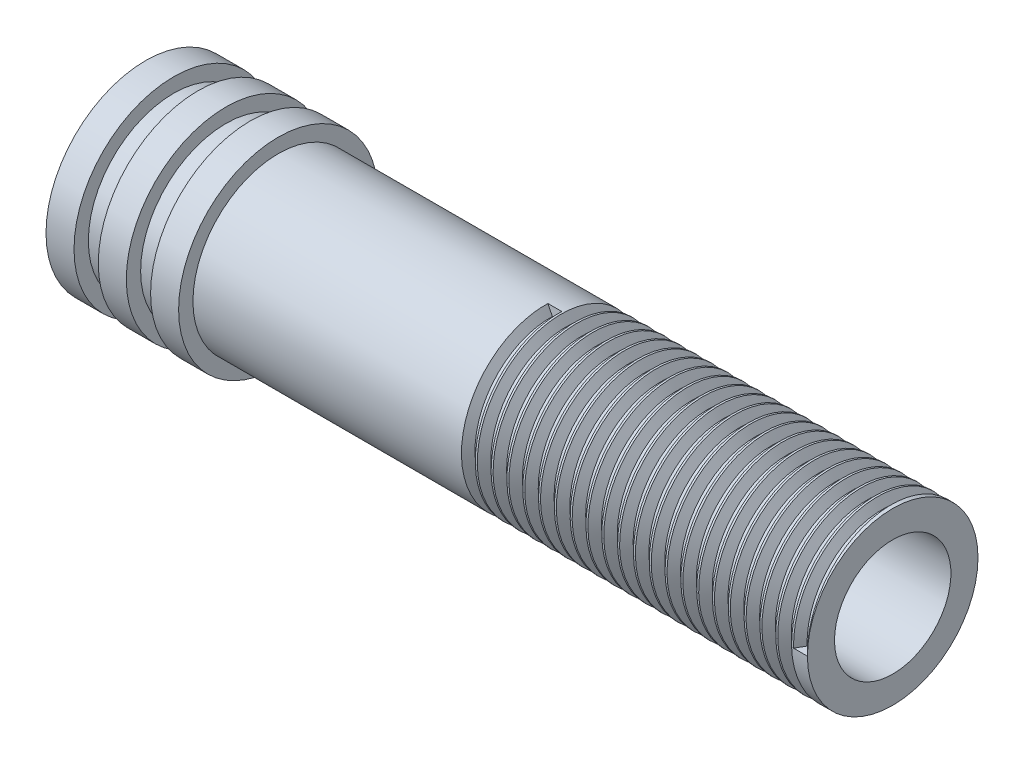
SolidWorks part; units mm, degrees
material "6061 Alloy"
ref_plane "Płaszczyzna przednia" through (0, 0, 0) normal (0, 0, 1) x (1, 0, 0)
ref_plane "Płaszczyzna górna" through (0, 0, 0) normal (0, 1, 0) x (1, 0, 0)
ref_plane "Płaszczyzna prawa" through (0, 0, 0) normal (1, 0, 0) x (0, 0, -1)
sketch "Szkic1" plane through (0, 0, 0) normal (0, 0, 1) x (1, 0, 0)
  line L0 (0, 0) -> (98.6784, 0)
  line L2 (10.7572, 0) -> (18.7572, 0)
  line L16 (72.2243, 0) -> (18.7572, 0)
  line L17 (-44.536, 13.7) -> (-44.536, 16.45)
  line L24 (-46.486, 13.7) -> (-42.586, 13.7)
  line L31 (0, 0) -> (-55.4823, 0)
  line L32 (-42.586, 13.7) -> (-42.586, 16)
  line L33 (-46.486, 13.7) -> (-46.486, 16)
  line L34 (-46.486, 16) -> (-50.986, 16)
  line L35 (-50.986, 16) -> (-50.986, 9.35)
  line L36 (-50.986, 9.35) -> (69.014, 9.35)
  line L37 (-29.686, 13.7) -> (69.014, 13.7)
  line L38 (-42.586, 16) -> (-38.086, 16)
  line L39 (-38.086, 16) -> (-38.086, 13.7)
  line L40 (-38.086, 13.7) -> (-34.186, 13.7)
  line L41 (-34.186, 13.7) -> (-34.186, 16)
  line L42 (-34.186, 16) -> (-29.686, 16)
  line L43 (-29.686, 16) -> (-29.686, 13.7)
  line L44 (69.014, 13.7) -> (69.014, 9.35)
  dimension "D1" = 120
  dimension "D2" = 6.65
  dimension "D4" = 3.9
  dimension "D9" = 9.35
  dimension "D11" = 2.3
  dimension "D5" = 4.5
  dimension "D6" = 3.9
  dimension "D7" = 2.3
  dimension "D8" = 2.3
  dimension "D10" = 2.3
  dimension "4,5" = 4.5
revolve "Obrót1" add sketch "Szkic1" angle 360 about L0
thread "Gwint1" pitch 2.54 method cut profile "Profil gwintu1" start angle 0, offset 0, length 54, pitch 2.54, diameter 27.4
ref_plane "Płaszczyzna1" through (69.014, 0, 13.7) normal (0, -1, 0) x (0, 0, 1)
sketch "Profil gwintu1" plane through (69.014, 0, 13.7) normal (0, -1, 0) x (0, 0, 1)
  line L0 (0, 0) -> (0, 2.54) construction
  line L11 (0, 0) -> (0, 2.2225)
  line L12 (0, 2.2225) -> (-1.3748, 1.4287)
  line L13 (-1.3748, 1.4287) -> (-1.3748, 0.7937)
  line L15 (-1.3748, 0.7937) -> (0, 0)
  line L17 (-1.3748, 1.1112) -> (0, 1.1112) construction
  point P2 (0, 0)
  dimension "Pitch" = 2.54
  dimension "Profile_Angle" = 60
  dimension "Profile_Land" = 0.635
  dimension "Profile_Height" = 1.3748
